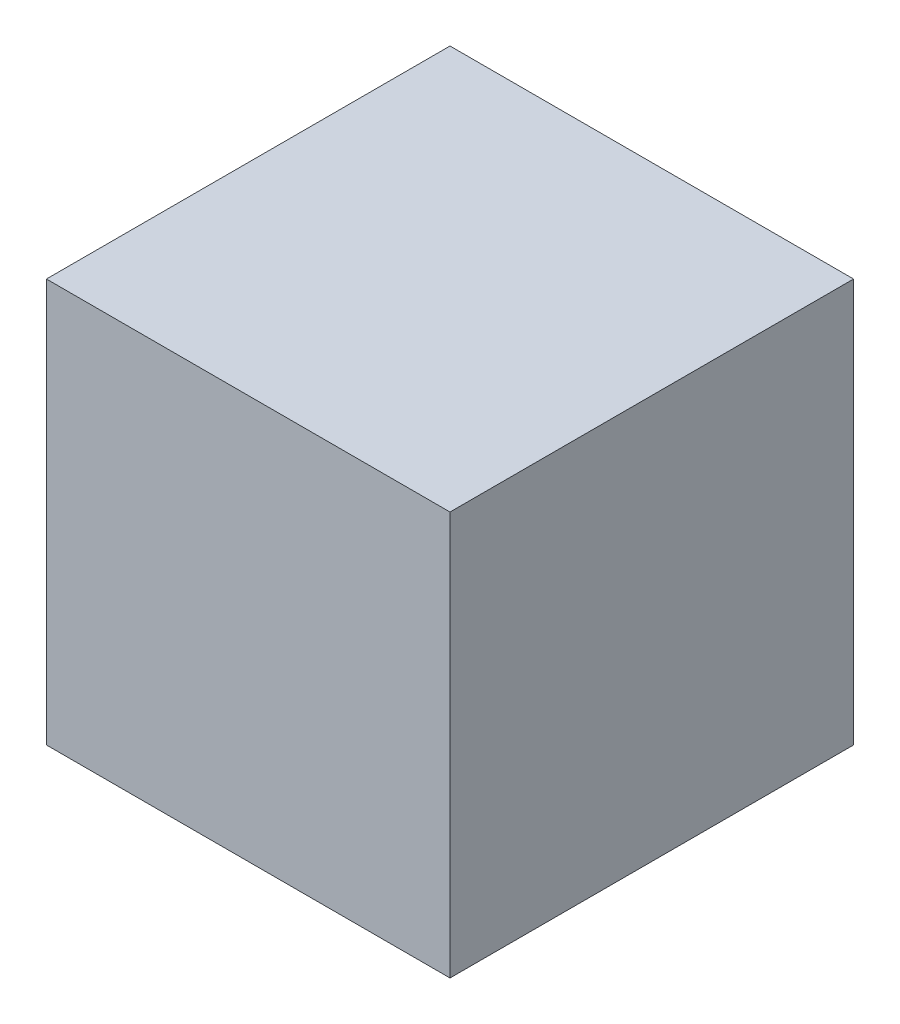
SolidWorks part; units mm, degrees
ref_plane "Ebene vorne" through (0, 0, 0) normal (0, 0, 1) x (1, 0, 0)
ref_plane "Ebene oben" through (0, 0, 0) normal (0, 1, 0) x (1, 0, 0)
ref_plane "Ebene rechts" through (0, 0, 0) normal (1, 0, 0) x (0, 0, -1)
sketch "Skizze1" plane through (0, 0, 0) normal (0, 0, 1) x (1, 0, 0)
  line L1 (0, 0) -> (70, 0)
  line L2 (0, 0) -> (0, 70)
  line L3 (0, 70) -> (70, 70)
  line L4 (70, 0) -> (70, 70)
  dimension "D1" = 70
  dimension "D2" = 70
extrude "Aufsatz-Linear austragen1" add sketch "Skizze1" along normal blind 70
